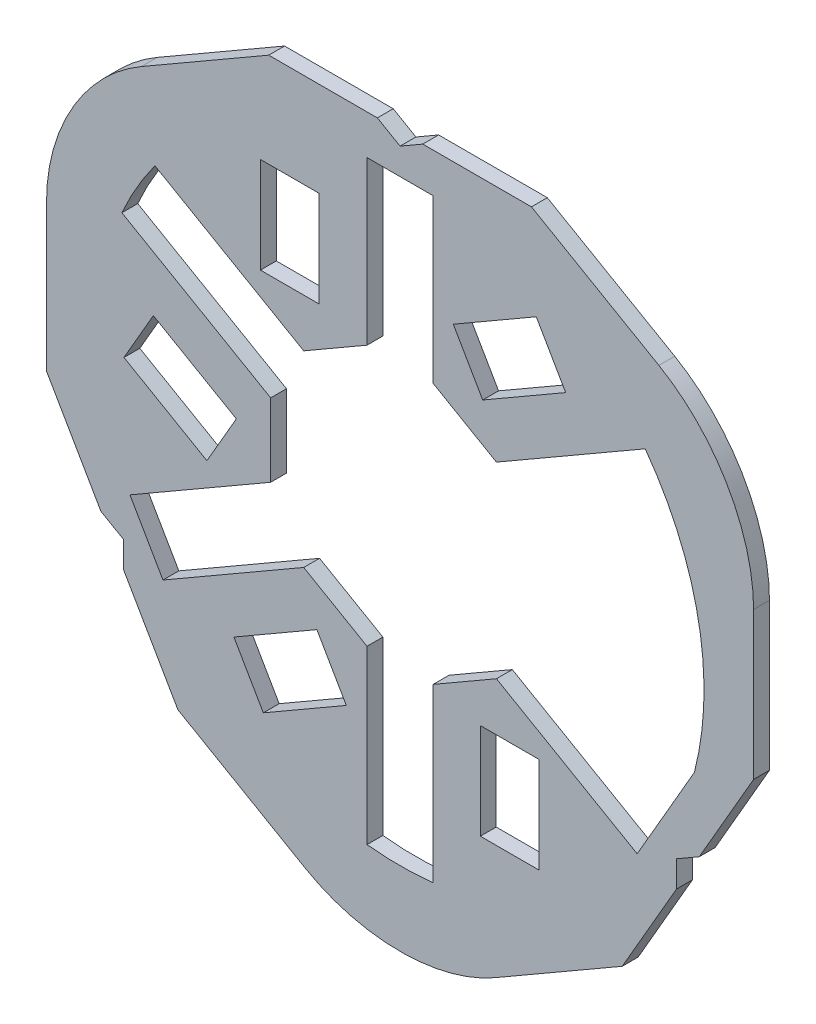
SolidWorks part; units mm, degrees
ref_plane "Front" through (0, 0, 0) normal (0, 0, 1) x (1, 0, 0)
ref_plane "Top" through (0, 0, 0) normal (0, 1, 0) x (1, 0, 0)
ref_plane "Right" through (0, 0, 0) normal (1, 0, 0) x (0, 0, -1)
sketch "Base sketch" plane through (0, 0, 0) normal (0, 0, 1) x (1, 0, 0)
  line L0 (7.1676, -26.75) -> (-7.1676, -26.75) construction
  line L1 (-19.7654, 19.7654) -> (-27, 7.2346) construction
  line L2 (-27, 7.2346) -> (-27, -7.2346) construction
  line L3 (-27, -7.2346) -> (-19.7654, -19.7654) construction
  line L4 (-19.7654, -19.7654) -> (-7.2346, -27) construction
  line L5 (-7.2346, -27) -> (7.2346, -27) construction
  line L6 (7.2346, -27) -> (19.7654, -19.7654) construction
  line L7 (19.7654, -19.7654) -> (27, -7.2346) construction
  line L8 (27, -7.2346) -> (27, 7.2346) construction
  line L9 (27, 7.2346) -> (19.7654, 19.7654) construction
  line L10 (19.7654, 19.7654) -> (7.2346, 27) construction
  line L11 (7.2346, 27) -> (-7.2346, 27) construction
  line L12 (-7.2346, 27) -> (-19.7654, 19.7654) construction
  line L13 (26.75, -3.9676) -> (26.75, 7.1676)
  line L14 (19.5824, 19.5824) -> (26.75, 7.1676) construction
  line L15 (19.5824, 19.5824) -> (9.9389, 25.15)
  line L16 (9.9389, 25.15) -> (1.717, 25.15)
  line L17 (26.75, -3.9676) -> (22.639, -11.088)
  line L18 (20.922, -14.062) -> (16.8111, -21.1824)
  line L19 (16.8111, -21.1824) -> (7.1676, -26.75)
  line L20 (-7.1676, -26.75) -> (-7.1308, -26.7813)
  line L21 (-7.1676, -26.75) -> (-16.8111, -21.1824)
  line L22 (-16.8111, -21.1824) -> (-20.922, -14.062)
  line L23 (-1.717, 25.15) -> (-9.9389, 25.15)
  line L24 (-9.9389, 25.15) -> (-19.5824, 19.5824)
  line L25 (-19.5824, 19.5824) -> (-26.75, 7.1676) construction
  line L26 (-26.75, 7.1676) -> (-26.75, -3.9676)
  line L27 (21.6506, 12.5) -> (0, 0) construction
  line L28 (0, 0) -> (0, -25) construction
  line L30 (-26.75, -3.9676) -> (-22.639, -11.088)
  line L35 (-10.0059, 25.4) -> (10.0059, 25.4) construction
  line L36 (0, 24.1587) -> (2.15, 25.4)
  line L37 (2.15, 25.4) -> (2.15, 27.8826)
  line L38 (2.15, 27.8826) -> (0, 29.1239)
  line L39 (0, 29.1239) -> (-2.15, 27.8826)
  line L40 (-2.15, 27.8826) -> (-2.15, 25.4)
  line L41 (-2.15, 25.4) -> (0, 24.1587)
  line L42 (-16.9941, -21.3654) -> (-27, -4.0346) construction
  line L43 (-20.922, -12.0793) -> (-23.072, -10.838)
  line L44 (-23.072, -10.838) -> (-25.222, -12.0793)
  line L45 (-25.222, -12.0793) -> (-25.222, -14.562)
  line L46 (-25.222, -14.562) -> (-23.072, -15.8033)
  line L47 (-23.072, -15.8033) -> (-20.922, -14.562)
  line L48 (-20.922, -14.562) -> (-20.922, -12.0793)
  line L49 (0, 0) -> (23.072, -13.3207) construction
  line L50 (20.922, -12.0793) -> (20.922, -14.562)
  line L51 (20.922, -14.562) -> (23.072, -15.8033)
  line L52 (23.072, -15.8033) -> (25.222, -14.562)
  line L53 (25.222, -14.562) -> (25.222, -12.0793)
  line L54 (25.222, -12.0793) -> (23.072, -10.838)
  line L55 (23.072, -10.838) -> (20.922, -12.0793)
  line L56 (16.9941, -21.3654) -> (27, -4.0346) construction
  circle A0 centre (0, 0) radius 25 construction
  circle A4 centre (0, 0) radius 27 construction
  circle A9 centre (0, 26.6413) radius 2.15 construction
  circle A11 centre (-23.072, -13.3207) radius 2.15 construction
  circle A13 centre (23.072, -13.3207) radius 2.15 construction
  conic Q0 (-27, 7.2346) -> (-19.7654, 19.7654) control (-27, 15.5885) rho 0.45 construction
  conic Q1 (-7.2346, 27) -> (7.2346, 27) control (0, 31.1769) rho 0.45 construction
  conic Q2 (19.7654, 19.7654) -> (27, 7.2346) control (27, 15.5885) rho 0.45 construction
  conic Q3 (27, -7.2346) -> (19.7654, -19.7654) control (27, -15.5885) rho 0.45 construction
  conic Q4 (7.2346, -27) -> (-7.2346, -27) control (0, -31.1769) rho 0.45 construction
  conic Q5 (-19.7654, -19.7654) -> (-27, -7.2346) control (-27, -15.5885) rho 0.45 construction
  conic Q6 (-19.5824, 19.5824) -> (-26.75, 7.1676) control (-26.75, 15.4441) rho 0.45
  conic Q7 (7.1676, -26.75) -> (-7.1676, -26.75) control (0, -30.8882) rho 0.45
  conic Q8 (19.5824, 19.5824) -> (26.75, 7.1676) control (26.75, 15.4441) rho 0.45
  point P15 (0, 0)
  point P51 (0, 0)
  point P53 (0, 0)
  point P77 (0, 0)
  point P89 (0, 0)
  point P97 (0, 25)
  point P99 (-21.6506, -12.5)
  point P111 (21.6506, -12.5)
  point P120 (0, 0)
  dimension "D1" = 50
  dimension "D4" = 54
  dimension "D19" = 120
  dimension "D26" = 4.3
  dimension "D27" = 0.4
  dimension "D29" = 0.4
  dimension "D30" = 4.3
  dimension "D32" = 4.3
  dimension "D34" = 0.4
  dimension "D11" = 0.25
  dimension "D12" = 0.25
  dimension "D14" = 0.25
  dimension "D15" = 0.25
  dimension "D16" = 0.25
  dimension "D17" = 0.25
  dimension "D21" = 0.25
  dimension "D24" = 0.25
  dimension "D28" = 0.25
  dimension "D31" = 0.25
  dimension "D35" = 0.25
  dimension "D36" = 0.25
  dimension "D25" = 0.25
  dimension "D20" = 0.25
  dimension "D13" = 0.25
extrude "Base" add sketch "Base sketch" along normal blind 1.2 contours L55 L17 L13 Q8 L15 L16 L36 L41 L23 L24 Q6 L26 L30 L43 L48 L22 L21 L19 L18 L50 region at (0, 0, 0)
sketch "PCB sketch" plane through (0, 0, 0) normal (0, 0, 1) x (1, 0, 0)
  line L0 (17.94, -13.2444) -> (22.2719, -5.7414)
  line L1 (-20.44, -8.9143) -> (-17.94, -13.2444)
  line L2 (-2.5, 22.1587) -> (2.5, 22.1587)
  line L27 (2.5, -22.8637) -> (2.5, -9.8637)
  line L28 (-2.5, -22.8637) -> (-2.5, -9.8637)
  line L29 (0.1, -0.0577) -> (-22.4167, 12.9423) construction
  line L30 (0, 0) -> (21.6506, 12.5) construction
  line L31 (18.5506, -13.5969) -> (7.2922, -7.0969)
  line L32 (-18.5506, -13.5969) -> (-7.2922, -7.0969)
  line L33 (-21.0506, -9.2668) -> (-9.7922, -2.7668)
  line L34 (2.5, 22.8637) -> (2.5, 9.8637)
  line L35 (-2.5, 22.8637) -> (-2.5, 9.8637)
  line L36 (-18.5506, 13.5969) -> (-7.2922, 7.0969)
  line L37 (-21.0506, 9.2668) -> (-9.7922, 2.7668)
  line L38 (18.5506, 13.5969) -> (7.2922, 7.0969)
  line L39 (7.2922, 7.0969) -> (2.5, 9.8637)
  line L40 (-2.5, 9.8637) -> (-7.2922, 7.0969)
  line L41 (-9.7922, 2.7668) -> (-9.7922, -2.7668)
  line L42 (-2.5, -9.8637) -> (-7.2922, -7.0969)
  line L43 (2.5, -9.8637) -> (7.2922, -7.0969)
  line L44 (-10.3476, -18.1514) -> (-12.5726, -14.2976)
  line L45 (10.525, -18.025) -> (6.075, -18.025)
  line L46 (10.525, -18.025) -> (10.525, -10.775)
  line L47 (10.525, -10.775) -> (6.075, -10.775)
  line L48 (6.075, -18.025) -> (6.075, -10.775)
  line L49 (-12.5726, -14.2976) -> (-6.2939, -10.6726)
  line L50 (-10.3476, -18.1514) -> (-4.0689, -14.5264)
  line L51 (-4.0689, -14.5264) -> (-6.2939, -10.6726)
  line L52 (-20.8934, -0.1384) -> (-18.6684, 3.7154)
  line L53 (-18.6684, 3.7154) -> (-12.3897, 0.0904)
  line L54 (-20.8934, -0.1384) -> (-14.6147, -3.7634)
  line L55 (-14.6147, -3.7634) -> (-12.3897, 0.0904)
  line L56 (-10.5665, 18.001) -> (-6.1165, 18.001)
  line L57 (-6.1165, 18.001) -> (-6.1165, 10.751)
  line L58 (-10.5665, 18.001) -> (-10.5665, 10.751)
  line L59 (-10.5665, 10.751) -> (-6.1165, 10.751)
  line L60 (10.3061, 18.1274) -> (12.5311, 14.2736)
  line L61 (12.5311, 14.2736) -> (6.2524, 10.6486)
  line L62 (10.3061, 18.1274) -> (4.0274, 14.5024)
  line L63 (4.0274, 14.5024) -> (6.2524, 10.6486)
  line L64 (20.8518, 0.1144) -> (18.6268, -3.7394)
  line L65 (18.6268, -3.7394) -> (12.3482, -0.1144)
  line L66 (20.8518, 0.1144) -> (14.5732, 3.7394)
  line L67 (14.5732, 3.7394) -> (12.3482, -0.1144)
  line L183 (-22.1753, 11.5437) -> (-21.9927, 11.5603) construction
  line L184 (-21.0848, 13.4325) -> (-21.0078, 13.2661) construction
  line L185 (21.0078, 13.2661) -> (21.0848, 13.4325) construction
  line L186 (21.9927, 11.5603) -> (22.1753, 11.5437) construction
  line L187 (-1.0905, -24.9762) -> (-0.9848, -24.8263) construction
  line L188 (0.9848, -24.8263) -> (1.0905, -24.9762) construction
  line L189 (3.3, -3.6) -> (3.3, -5.2) construction
  line L190 (4.1, -3.6) -> (4.1, -5.2) construction
  line L191 (3.3, -5.2) -> (4.1, -5.2) construction
  line L192 (3.3, -3.6) -> (4.1, -3.6) construction
  line L193 (-0.5, 7.7) -> (1.1, 7.7) construction
  line L194 (-0.5, 6.9) -> (1.1, 6.9) construction
  line L195 (-0.5, 7.7) -> (-0.5, 6.9) construction
  line L196 (1.1, 7.7) -> (1.1, 6.9) construction
  line L197 (-5.9, 4.9) -> (-5.9, 3.3) construction
  line L198 (-5.1, 4.9) -> (-5.1, 3.3) construction
  line L199 (-5.9, 3.3) -> (-5.1, 3.3) construction
  line L200 (-5.9, 4.9) -> (-5.1, 4.9) construction
  line L201 (-6.7, 0.5) -> (-5.1, 0.5) construction
  line L202 (-6.7, 1.3) -> (-5.1, 1.3) construction
  line L203 (-5.1, 1.3) -> (-5.1, 0.5) construction
  line L204 (-6.7, 1.3) -> (-6.7, 0.5) construction
  line L205 (-5.6, -3) -> (-5.6, -4.6) construction
  line L206 (-6.4, -3) -> (-6.4, -4.6) construction
  line L207 (-6.4, -3) -> (-5.6, -3) construction
  line L208 (-6.4, -4.6) -> (-5.6, -4.6) construction
  line L209 (5.65, -2.95) -> (5.65, -4.55) construction
  line L210 (4.85, -2.95) -> (4.85, -4.55) construction
  line L211 (4.85, -2.95) -> (5.65, -2.95) construction
  line L212 (4.85, -4.55) -> (5.65, -4.55) construction
  line L213 (4.7, 0) -> (4.7, -1.6) construction
  line L214 (5.5, 0) -> (5.5, -1.6) construction
  line L215 (4.7, -1.6) -> (5.5, -1.6) construction
  line L216 (4.7, 0) -> (5.5, 0) construction
  line L217 (2.8, 2.4) -> (4.4, 2.4) construction
  line L218 (2.8, 1.6) -> (4.4, 1.6) construction
  line L219 (2.8, 2.4) -> (2.8, 1.6) construction
  line L220 (4.4, 2.4) -> (4.4, 1.6) construction
  line L221 (5.05, 4.4) -> (6.65, 4.4) construction
  line L222 (5.05, 3.6) -> (6.65, 3.6) construction
  line L223 (5.05, 4.4) -> (5.05, 3.6) construction
  line L224 (6.65, 4.4) -> (6.65, 3.6) construction
  line L225 (7.5, 4.075) -> (7.5, -4.075) construction
  line L226 (7.5, 4.075) -> (10.35, 4.075) construction
  line L227 (7.5, -4.075) -> (10.35, -4.075) construction
  line L228 (10.35, 4.075) -> (10.35, -4.075) construction
  line L229 (7.6052, 12.3534) -> (10.4198, 13.9784) construction
  line L230 (6.1802, 14.8216) -> (7.6052, 12.3534) construction
  line L231 (6.1802, 14.8216) -> (8.9948, 16.4466) construction
  line L232 (8.9948, 16.4466) -> (10.4198, 13.9784) construction
  line L233 (6.2144, 14.8125) -> (7.6144, 12.3876) construction
  line L234 (8.9856, 16.4125) -> (10.3856, 13.9876) construction
  line L235 (7.6144, 12.3876) -> (10.3856, 13.9876) construction
  line L236 (6.2144, 14.8125) -> (8.9856, 16.4125) construction
  line L237 (-6.875, 16.025) -> (-6.875, 12.775) construction
  line L238 (-9.725, 12.775) -> (-6.875, 12.775) construction
  line L239 (-9.725, 16.025) -> (-9.725, 12.775) construction
  line L240 (-9.725, 16.025) -> (-6.875, 16.025) construction
  line L241 (-9.7, 12.8) -> (-6.9, 12.8) construction
  line L242 (-9.7, 16) -> (-6.9, 16) construction
  line L243 (-6.9, 16) -> (-6.9, 12.8) construction
  line L244 (-9.7, 16) -> (-9.7, 12.8) construction
  line L245 (-17.2948, 2.0466) -> (-14.4802, 0.4216) construction
  line L246 (-15.9052, -2.0466) -> (-14.4802, 0.4216) construction
  line L247 (-18.7198, -0.4216) -> (-15.9052, -2.0466) construction
  line L248 (-18.7198, -0.4216) -> (-17.2948, 2.0466) construction
  line L249 (-15.9144, -2.0124) -> (-14.5144, 0.4125) construction
  line L250 (-18.6856, -0.4124) -> (-17.2856, 2.0125) construction
  line L251 (-17.2856, 2.0125) -> (-14.5144, 0.4125) construction
  line L252 (-18.6856, -0.4124) -> (-15.9144, -2.0124) construction
  line L253 (-10.4198, -13.9784) -> (-7.6052, -12.3534) construction
  line L254 (-7.6052, -12.3534) -> (-6.1802, -14.8216) construction
  line L255 (-8.9948, -16.4466) -> (-6.1802, -14.8216) construction
  line L256 (-10.4198, -13.9784) -> (-8.9948, -16.4466) construction
  line L257 (-7.6144, -12.3875) -> (-6.2144, -14.8124) construction
  line L258 (-10.3856, -13.9875) -> (-8.9856, -16.4124) construction
  line L259 (-10.3856, -13.9875) -> (-7.6144, -12.3875) construction
  line L260 (-8.9856, -16.4124) -> (-6.2144, -14.8124) construction
  line L261 (6.875, -12.775) -> (6.875, -16.025) construction
  line L262 (6.875, -12.775) -> (9.725, -12.775) construction
  line L263 (9.725, -12.775) -> (9.725, -16.025) construction
  line L264 (6.875, -16.025) -> (9.725, -16.025) construction
  line L265 (6.9, -12.8) -> (9.7, -12.8) construction
  line L266 (6.9, -16) -> (9.7, -16) construction
  line L267 (6.9, -12.8) -> (6.9, -16) construction
  line L268 (9.7, -12.8) -> (9.7, -16) construction
  line L269 (14.4802, -0.4216) -> (17.2948, -2.0466) construction
  line L270 (14.4802, -0.4216) -> (15.9052, 2.0466) construction
  line L271 (15.9052, 2.0466) -> (18.7198, 0.4216) construction
  line L272 (17.2948, -2.0466) -> (18.7198, 0.4216) construction
  line L273 (14.5144, -0.4124) -> (15.9144, 2.0125) construction
  line L274 (17.2856, -2.0124) -> (18.6856, 0.4125) construction
  line L275 (14.5144, -0.4124) -> (17.2856, -2.0124) construction
  line L276 (15.9144, 2.0125) -> (18.6856, 0.4125) construction
  line L277 (-4.05, 4.75) -> (-4.05, 1.65) construction
  line L278 (-4.05, 4.75) -> (-0.95, 4.75) construction
  line L279 (-0.95, 4.75) -> (-0.95, 1.65) construction
  line L280 (-4.05, 1.65) -> (-0.95, 1.65) construction
  line L281 (12.2072, 8.0464) -> (13.5928, 8.8464) construction
  line L282 (12.6072, 7.3536) -> (13.9928, 8.1536) construction
  line L283 (12.2072, 8.0464) -> (12.6072, 7.3536) construction
  line L284 (13.5928, 8.8464) -> (13.9928, 8.1536) construction
  line L285 (15.5072, 9.0536) -> (16.8928, 9.8536) construction
  line L286 (15.1072, 9.7464) -> (16.4928, 10.5464) construction
  line L287 (16.4928, 10.5464) -> (16.8928, 9.8536) construction
  line L288 (15.1072, 9.7464) -> (15.5072, 9.0536) construction
  line L289 (9.0072, 5.2536) -> (10.3928, 6.0536) construction
  line L290 (8.6072, 5.9464) -> (9.9928, 6.7464) construction
  line L291 (9.9928, 6.7464) -> (10.3928, 6.0536) construction
  line L292 (8.6072, 5.9464) -> (9.0072, 5.2536) construction
  line L293 (-0.8, 16.6) -> (-0.8, 15) construction
  line L294 (0, 16.6) -> (0, 15) construction
  line L295 (-0.8, 15) -> (0, 15) construction
  line L296 (-0.8, 16.6) -> (0, 16.6) construction
  line L297 (0, 19.6) -> (0, 18) construction
  line L298 (-0.8, 19.6) -> (-0.8, 18) construction
  line L299 (-0.8, 19.6) -> (0, 19.6) construction
  line L300 (-0.8, 18) -> (0, 18) construction
  line L301 (0, 11.9) -> (0, 10.3) construction
  line L302 (-0.8, 11.9) -> (-0.8, 10.3) construction
  line L303 (-0.8, 11.9) -> (0, 11.9) construction
  line L304 (-0.8, 10.3) -> (0, 10.3) construction
  line L305 (-0.5, -8.125) -> (-0.5, -9.725) construction
  line L306 (0.3, -8.125) -> (0.3, -9.725) construction
  line L307 (-0.5, -9.725) -> (0.3, -9.725) construction
  line L308 (-0.5, -8.125) -> (0.3, -8.125) construction
  line L309 (-14.7928, 7.5536) -> (-13.4072, 6.7536) construction
  line L310 (-14.3928, 8.2464) -> (-13.0072, 7.4464) construction
  line L311 (-13.4072, 6.7536) -> (-13.0072, 7.4464) construction
  line L312 (-14.7928, 7.5536) -> (-14.3928, 8.2464) construction
  line L313 (-16.9928, 9.7464) -> (-15.6072, 8.9464) construction
  line L314 (-17.3928, 9.0536) -> (-16.0072, 8.2536) construction
  line L315 (-17.3928, 9.0536) -> (-16.9928, 9.7464) construction
  line L316 (-16.0072, 8.2536) -> (-15.6072, 8.9464) construction
  line L317 (-10.3928, 5.9464) -> (-9.0072, 5.1464) construction
  line L318 (-10.7928, 5.2536) -> (-9.4072, 4.4536) construction
  line L319 (-10.7928, 5.2536) -> (-10.3928, 5.9464) construction
  line L320 (-9.4072, 4.4536) -> (-9.0072, 5.1464) construction
  line L321 (-13.8928, -9.0464) -> (-12.5072, -8.2464) construction
  line L322 (-14.2928, -8.3536) -> (-12.9072, -7.5536) construction
  line L323 (-12.9072, -7.5536) -> (-12.5072, -8.2464) construction
  line L324 (-14.2928, -8.3536) -> (-13.8928, -9.0464) construction
  line L325 (-16.8928, -9.8536) -> (-15.5072, -9.0536) construction
  line L326 (-16.4928, -10.5464) -> (-15.1072, -9.7464) construction
  line L327 (-16.8928, -9.8536) -> (-16.4928, -10.5464) construction
  line L328 (-15.5072, -9.0536) -> (-15.1072, -9.7464) construction
  line L329 (-10.4928, -6.1536) -> (-9.1072, -5.3536) construction
  line L330 (-10.0928, -6.8464) -> (-8.7072, -6.0464) construction
  line L331 (-10.4928, -6.1536) -> (-10.0928, -6.8464) construction
  line L332 (-9.1072, -5.3536) -> (-8.7072, -6.0464) construction
  line L333 (0.9, -14.9) -> (0.9, -16.5) construction
  line L334 (0.1, -14.9) -> (0.1, -16.5) construction
  line L335 (0.1, -14.9) -> (0.9, -14.9) construction
  line L336 (0.1, -16.5) -> (0.9, -16.5) construction
  line L337 (0.1, -17.9) -> (0.1, -19.5) construction
  line L338 (0.9, -17.9) -> (0.9, -19.5) construction
  line L339 (0.1, -19.5) -> (0.9, -19.5) construction
  line L340 (0.1, -17.9) -> (0.9, -17.9) construction
  line L341 (0.1, -11.1) -> (0.1, -12.7) construction
  line L342 (0.9, -11.1) -> (0.9, -12.7) construction
  line L343 (0.1, -12.7) -> (0.9, -12.7) construction
  line L344 (0.1, -11.1) -> (0.9, -11.1) construction
  line L345 (13.4072, -6.8536) -> (14.7928, -7.6536) construction
  line L346 (13.0072, -7.5464) -> (14.3928, -8.3464) construction
  line L347 (13.0072, -7.5464) -> (13.4072, -6.8536) construction
  line L348 (14.3928, -8.3464) -> (14.7928, -7.6536) construction
  line L349 (15.6072, -9.0464) -> (16.9928, -9.8464) construction
  line L350 (16.0072, -8.3536) -> (17.3928, -9.1536) construction
  line L351 (16.9928, -9.8464) -> (17.3928, -9.1536) construction
  line L352 (15.6072, -9.0464) -> (16.0072, -8.3536) construction
  line L353 (8.9072, -5.5964) -> (10.2928, -6.3964) construction
  line L354 (9.3072, -4.9036) -> (10.6928, -5.7036) construction
  line L355 (10.2928, -6.3964) -> (10.6928, -5.7036) construction
  line L356 (8.9072, -5.5964) -> (9.3072, -4.9036) construction
  line L357 (0.175, 4.275) -> (1.775, 4.275) construction
  line L358 (0.175, 3.475) -> (1.775, 3.475) construction
  line L359 (0.175, 4.275) -> (0.175, 3.475) construction
  line L360 (1.775, 4.275) -> (1.775, 3.475) construction
  line L361 (-3.875, -6.075) -> (1.275, -6.075) construction
  line L362 (-3.875, -0.925) -> (-3.875, -6.075) construction
  line L363 (-3.875, -0.925) -> (1.275, -0.925) construction
  line L364 (1.275, -0.925) -> (1.275, -6.075) construction
  circle A4 centre (0, 0) radius 23
  circle A296 centre (4.7, 0) radius 0.025 construction
  circle A297 centre (5.5, 0) radius 0.025 construction
  circle A300 centre (5.5, 0) radius 0.025 construction
  circle A302 centre (4.7, 0) radius 0.025 construction
  circle A382 centre (-21.0848, 13.4325) radius 0.025 construction
  circle A383 centre (21.0848, 13.4325) radius 0.025 construction
  arc A384 (-21.0848, 13.4325) -> (21.0848, 13.4325) centre (0, 0) cw construction
  circle A385 centre (-1.0905, -24.9762) radius 0.025 construction
  circle A386 centre (-22.1753, 11.5437) radius 0.025 construction
  arc A387 (-1.0905, -24.9762) -> (-22.1753, 11.5437) centre (0, 0) cw construction
  circle A388 centre (22.1753, 11.5437) radius 0.025 construction
  circle A389 centre (1.0905, -24.9762) radius 0.025 construction
  arc A390 (22.1753, 11.5437) -> (1.0905, -24.9762) centre (0, 0) cw construction
  circle A391 centre (-21.0078, 13.2661) radius 0.025 construction
  circle A392 centre (-21.9927, 11.5603) radius 0.025 construction
  arc A393 (-21.0078, 13.2661) -> (-21.9927, 11.5603) centre (-21.6506, 12.5) cw construction
  circle A394 centre (-0.9848, -24.8263) radius 0.025 construction
  circle A395 centre (0.9848, -24.8263) radius 0.025 construction
  arc A396 (-0.9848, -24.8263) -> (0.9848, -24.8263) centre (0, -25) cw construction
  circle A397 centre (21.9927, 11.5603) radius 0.025 construction
  circle A398 centre (21.0078, 13.2661) radius 0.025 construction
  arc A399 (21.9927, 11.5603) -> (21.0078, 13.2661) centre (21.6506, 12.5) cw construction
  circle A400 centre (-21.9927, 11.5603) radius 0.025 construction
  circle A401 centre (-22.1753, 11.5437) radius 0.025 construction
  circle A402 centre (-21.0078, 13.2661) radius 0.025 construction
  circle A403 centre (-21.0848, 13.4325) radius 0.025 construction
  circle A404 centre (21.0848, 13.4325) radius 0.025 construction
  circle A405 centre (21.0078, 13.2661) radius 0.025 construction
  circle A406 centre (22.1753, 11.5437) radius 0.025 construction
  circle A407 centre (21.9927, 11.5603) radius 0.025 construction
  circle A408 centre (-0.9848, -24.8263) radius 0.025 construction
  circle A409 centre (-1.0905, -24.9762) radius 0.025 construction
  circle A410 centre (1.0905, -24.9762) radius 0.025 construction
  circle A411 centre (0.9848, -24.8263) radius 0.025 construction
  circle A412 centre (3.3, -5.2) radius 0.025 construction
  circle A413 centre (3.3, -3.6) radius 0.025 construction
  circle A414 centre (4.1, -5.2) radius 0.025 construction
  circle A415 centre (4.1, -3.6) radius 0.025 construction
  circle A416 centre (4.1, -5.2) radius 0.025 construction
  circle A417 centre (3.3, -5.2) radius 0.025 construction
  circle A418 centre (4.1, -3.6) radius 0.025 construction
  circle A419 centre (3.3, -3.6) radius 0.025 construction
  circle A420 centre (1.1, 7.7) radius 0.025 construction
  circle A421 centre (-0.5, 7.7) radius 0.025 construction
  circle A422 centre (1.1, 6.9) radius 0.025 construction
  circle A423 centre (-0.5, 6.9) radius 0.025 construction
  circle A424 centre (-0.5, 6.9) radius 0.025 construction
  circle A425 centre (-0.5, 7.7) radius 0.025 construction
  circle A426 centre (1.1, 6.9) radius 0.025 construction
  circle A427 centre (1.1, 7.7) radius 0.025 construction
  circle A428 centre (-5.9, 3.3) radius 0.025 construction
  circle A429 centre (-5.9, 4.9) radius 0.025 construction
  circle A430 centre (-5.1, 3.3) radius 0.025 construction
  circle A431 centre (-5.1, 4.9) radius 0.025 construction
  circle A432 centre (-5.1, 3.3) radius 0.025 construction
  circle A433 centre (-5.9, 3.3) radius 0.025 construction
  circle A434 centre (-5.1, 4.9) radius 0.025 construction
  circle A435 centre (-5.9, 4.9) radius 0.025 construction
  circle A436 centre (-5.1, 0.5) radius 0.025 construction
  circle A437 centre (-6.7, 0.5) radius 0.025 construction
  circle A438 centre (-5.1, 1.3) radius 0.025 construction
  circle A439 centre (-6.7, 1.3) radius 0.025 construction
  circle A440 centre (-5.1, 0.5) radius 0.025 construction
  circle A441 centre (-5.1, 1.3) radius 0.025 construction
  circle A442 centre (-6.7, 0.5) radius 0.025 construction
  circle A443 centre (-6.7, 1.3) radius 0.025 construction
  circle A444 centre (-5.6, -4.6) radius 0.025 construction
  circle A445 centre (-5.6, -3) radius 0.025 construction
  circle A446 centre (-6.4, -4.6) radius 0.025 construction
  circle A447 centre (-6.4, -3) radius 0.025 construction
  circle A448 centre (-5.6, -3) radius 0.025 construction
  circle A449 centre (-6.4, -3) radius 0.025 construction
  circle A450 centre (-5.6, -4.6) radius 0.025 construction
  circle A451 centre (-6.4, -4.6) radius 0.025 construction
  circle A452 centre (5.65, -4.55) radius 0.025 construction
  circle A453 centre (5.65, -2.95) radius 0.025 construction
  circle A454 centre (4.85, -4.55) radius 0.025 construction
  circle A455 centre (4.85, -2.95) radius 0.025 construction
  circle A456 centre (5.65, -2.95) radius 0.025 construction
  circle A457 centre (4.85, -2.95) radius 0.025 construction
  circle A458 centre (5.65, -4.55) radius 0.025 construction
  circle A459 centre (4.85, -4.55) radius 0.025 construction
  circle A460 centre (4.7, -1.6) radius 0.025 construction
  circle A461 centre (5.5, -1.6) radius 0.025 construction
  circle A462 centre (5.5, -1.6) radius 0.025 construction
  circle A463 centre (4.7, -1.6) radius 0.025 construction
  circle A464 centre (4.4, 2.4) radius 0.025 construction
  circle A465 centre (2.8, 2.4) radius 0.025 construction
  circle A466 centre (4.4, 1.6) radius 0.025 construction
  circle A467 centre (2.8, 1.6) radius 0.025 construction
  circle A468 centre (2.8, 1.6) radius 0.025 construction
  circle A469 centre (2.8, 2.4) radius 0.025 construction
  circle A470 centre (4.4, 1.6) radius 0.025 construction
  circle A471 centre (4.4, 2.4) radius 0.025 construction
  circle A472 centre (6.65, 4.4) radius 0.025 construction
  circle A473 centre (5.05, 4.4) radius 0.025 construction
  circle A474 centre (6.65, 3.6) radius 0.025 construction
  circle A475 centre (5.05, 3.6) radius 0.025 construction
  circle A476 centre (5.05, 3.6) radius 0.025 construction
  circle A477 centre (5.05, 4.4) radius 0.025 construction
  circle A478 centre (6.65, 3.6) radius 0.025 construction
  circle A479 centre (6.65, 4.4) radius 0.025 construction
  circle A480 centre (7.5, -4.075) radius 0.025 construction
  circle A481 centre (7.5, 4.075) radius 0.025 construction
  circle A482 centre (10.35, 4.075) radius 0.025 construction
  circle A483 centre (7.5, 4.075) radius 0.025 construction
  circle A484 centre (10.35, -4.075) radius 0.025 construction
  circle A485 centre (7.5, -4.075) radius 0.025 construction
  circle A486 centre (10.35, -4.075) radius 0.025 construction
  circle A487 centre (10.35, 4.075) radius 0.025 construction
  circle A488 centre (10.4198, 13.9784) radius 0.025 construction
  circle A489 centre (7.6052, 12.3534) radius 0.025 construction
  circle A490 centre (7.6052, 12.3534) radius 0.025 construction
  circle A491 centre (6.1802, 14.8216) radius 0.025 construction
  circle A492 centre (8.9948, 16.4466) radius 0.025 construction
  circle A493 centre (6.1802, 14.8216) radius 0.025 construction
  circle A494 centre (10.4198, 13.9784) radius 0.025 construction
  circle A495 centre (8.9948, 16.4466) radius 0.025 construction
  circle A496 centre (7.6144, 12.3876) radius 0.025 construction
  circle A497 centre (6.2144, 14.8125) radius 0.025 construction
  circle A498 centre (10.3856, 13.9876) radius 0.025 construction
  circle A499 centre (8.9856, 16.4125) radius 0.025 construction
  circle A500 centre (10.3856, 13.9876) radius 0.025 construction
  circle A501 centre (7.6144, 12.3876) radius 0.025 construction
  circle A502 centre (8.9856, 16.4125) radius 0.025 construction
  circle A503 centre (6.2144, 14.8125) radius 0.025 construction
  circle A504 centre (-6.875, 12.775) radius 0.025 construction
  circle A505 centre (-6.875, 16.025) radius 0.025 construction
  circle A506 centre (-6.875, 12.775) radius 0.025 construction
  circle A507 centre (-9.725, 12.775) radius 0.025 construction
  circle A508 centre (-9.725, 12.775) radius 0.025 construction
  circle A509 centre (-9.725, 16.025) radius 0.025 construction
  circle A510 centre (-6.875, 16.025) radius 0.025 construction
  circle A511 centre (-9.725, 16.025) radius 0.025 construction
  circle A512 centre (-6.9, 12.8) radius 0.025 construction
  circle A513 centre (-9.7, 12.8) radius 0.025 construction
  circle A514 centre (-6.9, 16) radius 0.025 construction
  circle A515 centre (-9.7, 16) radius 0.025 construction
  circle A516 centre (-6.9, 12.8) radius 0.025 construction
  circle A517 centre (-6.9, 16) radius 0.025 construction
  circle A518 centre (-9.7, 12.8) radius 0.025 construction
  circle A519 centre (-9.7, 16) radius 0.025 construction
  circle A520 centre (-14.4802, 0.4216) radius 0.025 construction
  circle A521 centre (-17.2948, 2.0466) radius 0.025 construction
  circle A522 centre (-14.4802, 0.4216) radius 0.025 construction
  circle A523 centre (-15.9052, -2.0466) radius 0.025 construction
  circle A524 centre (-15.9052, -2.0466) radius 0.025 construction
  circle A525 centre (-18.7198, -0.4216) radius 0.025 construction
  circle A526 centre (-17.2948, 2.0466) radius 0.025 construction
  circle A527 centre (-18.7198, -0.4216) radius 0.025 construction
  circle A528 centre (-14.5144, 0.4125) radius 0.025 construction
  circle A529 centre (-15.9144, -2.0124) radius 0.025 construction
  circle A530 centre (-17.2856, 2.0125) radius 0.025 construction
  circle A531 centre (-18.6856, -0.4124) radius 0.025 construction
  circle A532 centre (-14.5144, 0.4125) radius 0.025 construction
  circle A533 centre (-17.2856, 2.0125) radius 0.025 construction
  circle A534 centre (-15.9144, -2.0124) radius 0.025 construction
  circle A535 centre (-18.6856, -0.4124) radius 0.025 construction
  circle A536 centre (-7.6052, -12.3534) radius 0.025 construction
  circle A537 centre (-10.4198, -13.9784) radius 0.025 construction
  circle A538 centre (-6.1802, -14.8216) radius 0.025 construction
  circle A539 centre (-7.6052, -12.3534) radius 0.025 construction
  circle A540 centre (-6.1802, -14.8216) radius 0.025 construction
  circle A541 centre (-8.9948, -16.4466) radius 0.025 construction
  circle A542 centre (-8.9948, -16.4466) radius 0.025 construction
  circle A543 centre (-10.4198, -13.9784) radius 0.025 construction
  circle A544 centre (-6.2144, -14.8124) radius 0.025 construction
  circle A545 centre (-7.6144, -12.3875) radius 0.025 construction
  circle A546 centre (-8.9856, -16.4124) radius 0.025 construction
  circle A547 centre (-10.3856, -13.9875) radius 0.025 construction
  circle A548 centre (-7.6144, -12.3875) radius 0.025 construction
  circle A549 centre (-10.3856, -13.9875) radius 0.025 construction
  circle A550 centre (-6.2144, -14.8124) radius 0.025 construction
  circle A551 centre (-8.9856, -16.4124) radius 0.025 construction
  circle A552 centre (6.875, -16.025) radius 0.025 construction
  circle A553 centre (6.875, -12.775) radius 0.025 construction
  circle A554 centre (9.725, -12.775) radius 0.025 construction
  circle A555 centre (6.875, -12.775) radius 0.025 construction
  circle A556 centre (9.725, -16.025) radius 0.025 construction
  circle A557 centre (9.725, -12.775) radius 0.025 construction
  circle A558 centre (9.725, -16.025) radius 0.025 construction
  circle A559 centre (6.875, -16.025) radius 0.025 construction
  circle A560 centre (9.7, -12.8) radius 0.025 construction
  circle A561 centre (6.9, -12.8) radius 0.025 construction
  circle A562 centre (9.7, -16) radius 0.025 construction
  circle A563 centre (6.9, -16) radius 0.025 construction
  circle A564 centre (6.9, -16) radius 0.025 construction
  circle A565 centre (6.9, -12.8) radius 0.025 construction
  circle A566 centre (9.7, -16) radius 0.025 construction
  circle A567 centre (9.7, -12.8) radius 0.025 construction
  circle A568 centre (17.2948, -2.0466) radius 0.025 construction
  circle A569 centre (14.4802, -0.4216) radius 0.025 construction
  circle A570 centre (15.9052, 2.0466) radius 0.025 construction
  circle A571 centre (14.4802, -0.4216) radius 0.025 construction
  circle A572 centre (18.7198, 0.4216) radius 0.025 construction
  circle A573 centre (15.9052, 2.0466) radius 0.025 construction
  circle A574 centre (18.7198, 0.4216) radius 0.025 construction
  circle A575 centre (17.2948, -2.0466) radius 0.025 construction
  circle A576 centre (15.9144, 2.0125) radius 0.025 construction
  circle A577 centre (14.5144, -0.4124) radius 0.025 construction
  circle A578 centre (18.6856, 0.4125) radius 0.025 construction
  circle A579 centre (17.2856, -2.0124) radius 0.025 construction
  circle A580 centre (17.2856, -2.0124) radius 0.025 construction
  circle A581 centre (14.5144, -0.4124) radius 0.025 construction
  circle A582 centre (18.6856, 0.4125) radius 0.025 construction
  circle A583 centre (15.9144, 2.0125) radius 0.025 construction
  circle A584 centre (-4.05, 1.65) radius 0.025 construction
  circle A585 centre (-4.05, 4.75) radius 0.025 construction
  circle A586 centre (-0.95, 4.75) radius 0.025 construction
  circle A587 centre (-4.05, 4.75) radius 0.025 construction
  circle A588 centre (-0.95, 1.65) radius 0.025 construction
  circle A589 centre (-0.95, 4.75) radius 0.025 construction
  circle A590 centre (-0.95, 1.65) radius 0.025 construction
  circle A591 centre (-4.05, 1.65) radius 0.025 construction
  circle A592 centre (13.5928, 8.8464) radius 0.025 construction
  circle A593 centre (12.2072, 8.0464) radius 0.025 construction
  circle A594 centre (13.9928, 8.1536) radius 0.025 construction
  circle A595 centre (12.6072, 7.3536) radius 0.025 construction
  circle A596 centre (12.6072, 7.3536) radius 0.025 construction
  circle A597 centre (12.2072, 8.0464) radius 0.025 construction
  circle A598 centre (13.9928, 8.1536) radius 0.025 construction
  circle A599 centre (13.5928, 8.8464) radius 0.025 construction
  circle A600 centre (16.8928, 9.8536) radius 0.025 construction
  circle A601 centre (15.5072, 9.0536) radius 0.025 construction
  circle A602 centre (16.4928, 10.5464) radius 0.025 construction
  circle A603 centre (15.1072, 9.7464) radius 0.025 construction
  circle A604 centre (16.8928, 9.8536) radius 0.025 construction
  circle A605 centre (16.4928, 10.5464) radius 0.025 construction
  circle A606 centre (15.5072, 9.0536) radius 0.025 construction
  circle A607 centre (15.1072, 9.7464) radius 0.025 construction
  circle A608 centre (10.3928, 6.0536) radius 0.025 construction
  circle A609 centre (9.0072, 5.2536) radius 0.025 construction
  circle A610 centre (9.9928, 6.7464) radius 0.025 construction
  circle A611 centre (8.6072, 5.9464) radius 0.025 construction
  circle A612 centre (10.3928, 6.0536) radius 0.025 construction
  circle A613 centre (9.9928, 6.7464) radius 0.025 construction
  circle A614 centre (9.0072, 5.2536) radius 0.025 construction
  circle A615 centre (8.6072, 5.9464) radius 0.025 construction
  circle A616 centre (-0.8, 15) radius 0.025 construction
  circle A617 centre (-0.8, 16.6) radius 0.025 construction
  circle A618 centre (0, 15) radius 0.025 construction
  circle A619 centre (0, 16.6) radius 0.025 construction
  circle A620 centre (0, 15) radius 0.025 construction
  circle A621 centre (-0.8, 15) radius 0.025 construction
  circle A622 centre (0, 16.6) radius 0.025 construction
  circle A623 centre (-0.8, 16.6) radius 0.025 construction
  circle A624 centre (0, 18) radius 0.025 construction
  circle A625 centre (0, 19.6) radius 0.025 construction
  circle A626 centre (-0.8, 18) radius 0.025 construction
  circle A627 centre (-0.8, 19.6) radius 0.025 construction
  circle A628 centre (0, 19.6) radius 0.025 construction
  circle A629 centre (-0.8, 19.6) radius 0.025 construction
  circle A630 centre (0, 18) radius 0.025 construction
  circle A631 centre (-0.8, 18) radius 0.025 construction
  circle A632 centre (0, 10.3) radius 0.025 construction
  circle A633 centre (0, 11.9) radius 0.025 construction
  circle A634 centre (-0.8, 10.3) radius 0.025 construction
  circle A635 centre (-0.8, 11.9) radius 0.025 construction
  circle A636 centre (0, 11.9) radius 0.025 construction
  circle A637 centre (-0.8, 11.9) radius 0.025 construction
  circle A638 centre (0, 10.3) radius 0.025 construction
  circle A639 centre (-0.8, 10.3) radius 0.025 construction
  circle A640 centre (-0.5, -9.725) radius 0.025 construction
  circle A641 centre (-0.5, -8.125) radius 0.025 construction
  circle A642 centre (0.3, -9.725) radius 0.025 construction
  circle A643 centre (0.3, -8.125) radius 0.025 construction
  circle A644 centre (0.3, -9.725) radius 0.025 construction
  circle A645 centre (-0.5, -9.725) radius 0.025 construction
  circle A646 centre (0.3, -8.125) radius 0.025 construction
  circle A647 centre (-0.5, -8.125) radius 0.025 construction
  circle A648 centre (-13.4072, 6.7536) radius 0.025 construction
  circle A649 centre (-14.7928, 7.5536) radius 0.025 construction
  circle A650 centre (-13.0072, 7.4464) radius 0.025 construction
  circle A651 centre (-14.3928, 8.2464) radius 0.025 construction
  circle A652 centre (-13.0072, 7.4464) radius 0.025 construction
  circle A653 centre (-13.4072, 6.7536) radius 0.025 construction
  circle A654 centre (-14.3928, 8.2464) radius 0.025 construction
  circle A655 centre (-14.7928, 7.5536) radius 0.025 construction
  circle A656 centre (-15.6072, 8.9464) radius 0.025 construction
  circle A657 centre (-16.9928, 9.7464) radius 0.025 construction
  circle A658 centre (-16.0072, 8.2536) radius 0.025 construction
  circle A659 centre (-17.3928, 9.0536) radius 0.025 construction
  circle A660 centre (-16.9928, 9.7464) radius 0.025 construction
  circle A661 centre (-17.3928, 9.0536) radius 0.025 construction
  circle A662 centre (-15.6072, 8.9464) radius 0.025 construction
  circle A663 centre (-16.0072, 8.2536) radius 0.025 construction
  circle A664 centre (-9.0072, 5.1464) radius 0.025 construction
  circle A665 centre (-10.3928, 5.9464) radius 0.025 construction
  circle A666 centre (-9.4072, 4.4536) radius 0.025 construction
  circle A667 centre (-10.7928, 5.2536) radius 0.025 construction
  circle A668 centre (-10.3928, 5.9464) radius 0.025 construction
  circle A669 centre (-10.7928, 5.2536) radius 0.025 construction
  circle A670 centre (-9.0072, 5.1464) radius 0.025 construction
  circle A671 centre (-9.4072, 4.4536) radius 0.025 construction
  circle A672 centre (-12.5072, -8.2464) radius 0.025 construction
  circle A673 centre (-13.8928, -9.0464) radius 0.025 construction
  circle A674 centre (-12.9072, -7.5536) radius 0.025 construction
  circle A675 centre (-14.2928, -8.3536) radius 0.025 construction
  circle A676 centre (-12.5072, -8.2464) radius 0.025 construction
  circle A677 centre (-12.9072, -7.5536) radius 0.025 construction
  circle A678 centre (-13.8928, -9.0464) radius 0.025 construction
  circle A679 centre (-14.2928, -8.3536) radius 0.025 construction
  circle A680 centre (-15.5072, -9.0536) radius 0.025 construction
  circle A681 centre (-16.8928, -9.8536) radius 0.025 construction
  circle A682 centre (-15.1072, -9.7464) radius 0.025 construction
  circle A683 centre (-16.4928, -10.5464) radius 0.025 construction
  circle A684 centre (-16.4928, -10.5464) radius 0.025 construction
  circle A685 centre (-16.8928, -9.8536) radius 0.025 construction
  circle A686 centre (-15.1072, -9.7464) radius 0.025 construction
  circle A687 centre (-15.5072, -9.0536) radius 0.025 construction
  circle A688 centre (-9.1072, -5.3536) radius 0.025 construction
  circle A689 centre (-10.4928, -6.1536) radius 0.025 construction
  circle A690 centre (-8.7072, -6.0464) radius 0.025 construction
  circle A691 centre (-10.0928, -6.8464) radius 0.025 construction
  circle A692 centre (-10.0928, -6.8464) radius 0.025 construction
  circle A693 centre (-10.4928, -6.1536) radius 0.025 construction
  circle A694 centre (-8.7072, -6.0464) radius 0.025 construction
  circle A695 centre (-9.1072, -5.3536) radius 0.025 construction
  circle A696 centre (0.9, -16.5) radius 0.025 construction
  circle A697 centre (0.9, -14.9) radius 0.025 construction
  circle A698 centre (0.1, -16.5) radius 0.025 construction
  circle A699 centre (0.1, -14.9) radius 0.025 construction
  circle A700 centre (0.9, -14.9) radius 0.025 construction
  circle A701 centre (0.1, -14.9) radius 0.025 construction
  circle A702 centre (0.9, -16.5) radius 0.025 construction
  circle A703 centre (0.1, -16.5) radius 0.025 construction
  circle A704 centre (0.1, -19.5) radius 0.025 construction
  circle A705 centre (0.1, -17.9) radius 0.025 construction
  circle A706 centre (0.9, -19.5) radius 0.025 construction
  circle A707 centre (0.9, -17.9) radius 0.025 construction
  circle A708 centre (0.9, -19.5) radius 0.025 construction
  circle A709 centre (0.1, -19.5) radius 0.025 construction
  circle A710 centre (0.9, -17.9) radius 0.025 construction
  circle A711 centre (0.1, -17.9) radius 0.025 construction
  circle A712 centre (0.1, -12.7) radius 0.025 construction
  circle A713 centre (0.1, -11.1) radius 0.025 construction
  circle A714 centre (0.9, -12.7) radius 0.025 construction
  circle A715 centre (0.9, -11.1) radius 0.025 construction
  circle A716 centre (0.9, -12.7) radius 0.025 construction
  circle A717 centre (0.1, -12.7) radius 0.025 construction
  circle A718 centre (0.9, -11.1) radius 0.025 construction
  circle A719 centre (0.1, -11.1) radius 0.025 construction
  circle A720 centre (14.7928, -7.6536) radius 0.025 construction
  circle A721 centre (13.4072, -6.8536) radius 0.025 construction
  circle A722 centre (14.3928, -8.3464) radius 0.025 construction
  circle A723 centre (13.0072, -7.5464) radius 0.025 construction
  circle A724 centre (13.4072, -6.8536) radius 0.025 construction
  circle A725 centre (13.0072, -7.5464) radius 0.025 construction
  circle A726 centre (14.7928, -7.6536) radius 0.025 construction
  circle A727 centre (14.3928, -8.3464) radius 0.025 construction
  circle A728 centre (16.9928, -9.8464) radius 0.025 construction
  circle A729 centre (15.6072, -9.0464) radius 0.025 construction
  circle A730 centre (17.3928, -9.1536) radius 0.025 construction
  circle A731 centre (16.0072, -8.3536) radius 0.025 construction
  circle A732 centre (17.3928, -9.1536) radius 0.025 construction
  circle A733 centre (16.9928, -9.8464) radius 0.025 construction
  circle A734 centre (16.0072, -8.3536) radius 0.025 construction
  circle A735 centre (15.6072, -9.0464) radius 0.025 construction
  circle A736 centre (10.2928, -6.3964) radius 0.025 construction
  circle A737 centre (8.9072, -5.5964) radius 0.025 construction
  circle A738 centre (10.6928, -5.7036) radius 0.025 construction
  circle A739 centre (9.3072, -4.9036) radius 0.025 construction
  circle A740 centre (10.6928, -5.7036) radius 0.025 construction
  circle A741 centre (10.2928, -6.3964) radius 0.025 construction
  circle A742 centre (9.3072, -4.9036) radius 0.025 construction
  circle A743 centre (8.9072, -5.5964) radius 0.025 construction
  circle A744 centre (1.775, 4.275) radius 0.025 construction
  circle A745 centre (0.175, 4.275) radius 0.025 construction
  circle A746 centre (1.775, 3.475) radius 0.025 construction
  circle A747 centre (0.175, 3.475) radius 0.025 construction
  circle A748 centre (0.175, 3.475) radius 0.025 construction
  circle A749 centre (0.175, 4.275) radius 0.025 construction
  circle A750 centre (1.775, 3.475) radius 0.025 construction
  circle A751 centre (1.775, 4.275) radius 0.025 construction
  circle A752 centre (1.275, -6.075) radius 0.025 construction
  circle A753 centre (-3.875, -6.075) radius 0.025 construction
  circle A754 centre (-3.875, -6.075) radius 0.025 construction
  circle A755 centre (-3.875, -0.925) radius 0.025 construction
  circle A756 centre (1.275, -0.925) radius 0.025 construction
  circle A757 centre (-3.875, -0.925) radius 0.025 construction
  circle A758 centre (1.275, -6.075) radius 0.025 construction
  circle A759 centre (1.275, -0.925) radius 0.025 construction
  point P34 (0, 0)
  point P96 (-0.0208, -0.012)
  dimension "D3" = 2
  dimension "D4" = 2.5
  dimension "D5" = 2.5
  dimension "D6" = 2
  dimension "D7" = 2.5
  dimension "D8" = 2.5
  dimension "D9" = 2.5
  dimension "D10" = 2
  dimension "D11" = 2
  dimension "D13" = 2.5
  dimension "D14" = 2.5
  dimension "D15" = 2.5
  dimension "D16" = 13
  dimension "D20" = 0.8
  dimension "D21" = 0.8
  dimension "D22" = 2
  dimension "D23" = 2
  dimension "D25" = 0.8
  dimension "D26" = 2
  dimension "D24" = 6
extrude "PCB Component room" cut sketch "PCB sketch" along normal through all contours L58 L59 L57 L56 | L34 A4 L35 L40 L36 L37 L41 L33 L32 L42 L28 L27 L43 L31 L38 L39 L67 L66 L64 L65 | L66 L67 L65 L64 | L48 L45 L46 L47 | L50 L51 L49 L44 | L62 L63 L61 L60 | L54 L55 L53 L52 region at (2.6794, 0.0143, 0) region at (-8.3208, -14.412, 0) region at (8.3, -14.4, 0) region at (-16.6415, -0.024, 0) region at (-8.3415, 14.376, 0) region at (8.2792, 14.388, 0) region at (16.6, 0, 0)
ref_axis "Central Z" through (0, 0, -9.0264) along (0, 0, 1)
chamfer "Removal room" distance 1 angle 45 1 edges at (22.5856, 4.3462, 0)
equation "\"pcb_diameter\"=50"
equation "\"D1@Base sketch\"=\"pcb_diameter\""
equation "\"pcb_room_total\"= 4"
equation "\"hull_conic_rho\"= 0.45"
equation "\"D4@Base sketch\"=\"pcb_diameter\"+\"pcb_room_total\""
equation "\"D5@Base sketch\"=\"hull_conic_rho\""
equation "\"D6@Base sketch\"=\"hull_conic_rho\""
equation "\"D7@Base sketch\"=\"hull_conic_rho\""
equation "\"D8@Base sketch\"=\"hull_conic_rho\""
equation "\"D9@Base sketch\"=\"hull_conic_rho\""
equation "\"D10@Base sketch\"=\"hull_conic_rho\""
equation "\"nut_size\"=4"
equation "\"D18@Base sketch\"=\"hull_conic_rho\""
equation "\"nut_thickness\"=1.6"
equation "\"top_pcb_cover_room\"= 0.25"
equation "\"pcb_side_room\"= 0.4"
equation "\"D22@Base sketch\"=\"hull_conic_rho\""
equation "\"D25@Base sketch\" = \"top_pcb_cover_room\""
equation "\"D26@Base sketch\"=\"nut_size\"+\"nut_room\"*2"
equation "\"D27@Base sketch\"=\"pcb_side_room\""
equation "\"D29@Base sketch\"=\"pcb_side_room\""
equation "\"D30@Base sketch\"=\"nut_size\"+\"nut_room\"*2"
equation "\"D32@Base sketch\"=\"pcb_room_total\"+\"nut_room\"*2"
equation "\"D34@Base sketch\" = \"pcb_side_room\""
equation "\"D11@Base sketch\"=\"top_pcb_cover_room\""
equation "\"D12@Base sketch\"=\"top_pcb_cover_room\""
equation "\"D13@Base sketch\"=\"top_pcb_cover_room\""
equation "\"D14@Base sketch\"=\"top_pcb_cover_room\""
equation "\"D15@Base sketch\"=\"top_pcb_cover_room\""
equation "\"D16@Base sketch\"=\"top_pcb_cover_room\""
equation "\"D17@Base sketch\"=\"top_pcb_cover_room\""
equation "\"D20@Base sketch\"=\"top_pcb_cover_room\""
equation "\"D21@Base sketch\"=\"top_pcb_cover_room\""
equation "\"D24@Base sketch\"=\"top_pcb_cover_room\""
equation "\"D28@Base sketch\"=\"top_pcb_cover_room\""
equation "\"D31@Base sketch\"=\"top_pcb_cover_room\""
equation "\"D33@Base sketch\"=\"hull_conic_rho\""
equation "\"D35@Base sketch\"=\"top_pcb_cover_room\""
equation "\"D36@Base sketch\"=\"top_pcb_cover_room\""
equation "\"D1@Base\"=1.0"
equation "\"nut_room\"=0.15"
